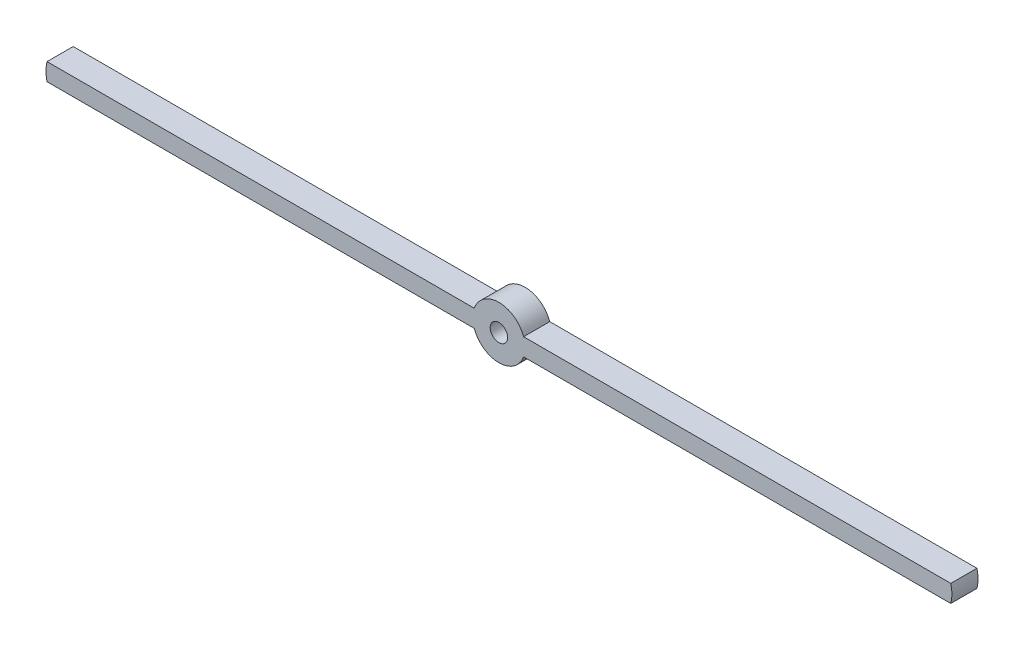
SolidWorks part; units mm, degrees
ref_plane "Plan de face" through (0, 0, 0) normal (0, 0, 1) x (1, 0, 0)
ref_plane "Plan de dessus" through (0, 0, 0) normal (0, 1, 0) x (1, 0, 0)
ref_plane "Plan de droite" through (0, 0, 0) normal (1, 0, 0) x (0, 0, -1)
sketch "Esquisse1" plane through (0, 0, 0) normal (0, 0, 1) x (1, 0, 0)
  line L1 (-5.6569, 2) -> (-103.6569, 2)
  line L2 (-5.6569, 2) -> (-5.6569, -2) construction
  line L3 (-5.6569, -2) -> (-103.6569, -2)
  line L4 (-103.6569, 2) -> (-103.6569, -2) construction
  line L5 (5.6569, 2) -> (103.6569, 2)
  line L6 (5.6569, 2) -> (5.6569, -2) construction
  line L7 (5.6569, -2) -> (103.6569, -2)
  line L8 (103.6569, 2) -> (103.6569, -2) construction
  circle A0 centre (0, 0) radius 2
  circle A1 centre (0, 0) radius 6 construction
  arc A2 (-103.6569, 2) -> (-103.6569, -2) centre (-95.9109, 0) ccw
  arc A3 (103.6569, 2) -> (103.6569, -2) centre (95.9109, 0) cw
  arc A4 (-5.6569, 2) -> (5.6569, 2) centre (0, 0) cw
  arc A5 (5.6569, -2) -> (-5.6569, -2) centre (0, 0) cw
  dimension "D1" = 4
  dimension "D5" = 8
  dimension "D2" = 4
  dimension "D3" = 4
  dimension "D4" = 98
extrude "Boss.-Extru.1" add sketch "Esquisse1" along normal blind 6 contours A0 | L3 A2 L1 A4 L5 A3 L7 A5 region at (0, 0, 0)
